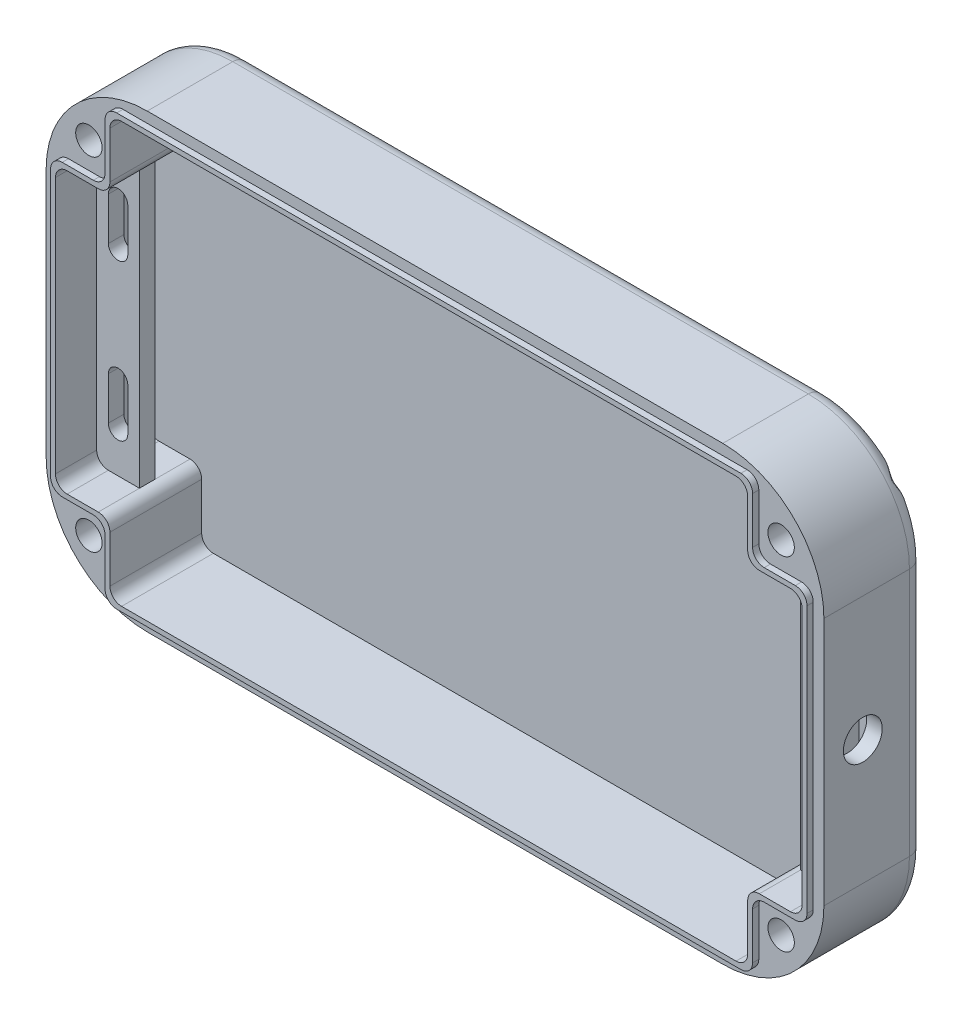
SolidWorks part; units mm, degrees
ref_plane "Спереди" through (0, 0, 0) normal (0, 0, 1) x (1, 0, 0)
ref_plane "Сверху" through (0, 0, 0) normal (0, 1, 0) x (1, 0, 0)
ref_plane "Справа" through (0, 0, 0) normal (1, 0, 0) x (0, 0, -1)
sketch "Sketch1" plane through (0, 0, 0) normal (0, 0, 1) x (1, 0, 0)
  line L1 (-50, 58) -> (50, 58) construction
  line L2 (-50, 58) -> (-50, 0) construction
  line L3 (-50, 0) -> (50, 0) construction
  line L5 (-50, 29) -> (30, 29) construction
  line L7 (0, 0) -> (0, 58) construction
  line L10 (-50, 58) -> (-50, 0) construction
  line L11 (-50, 58) -> (50, 58)
  line L12 (50, 58) -> (50, 0) construction
  line L13 (50, 0) -> (-50, 0)
  line L20 (50, 0) -> (50, 19)
  line L21 (50, 19) -> (50, 58)
  line L22 (-50, 0) -> (-50, 19)
  line L23 (-50, 19) -> (-50, 58)
  dimension "D1" = 100
  dimension "D2" = 58
extrude "Boss-Extrude1" add sketch "Sketch1" along normal blind 13
shell "Shell1" thickness 2 removed face at (0, 29, 13)
sketch "Sketch3" plane through (0, 0, 2) normal (0, 0, 1) x (1, 0, 0)
  line L0 (0, 0) -> (0, 58) construction
  line L1 (48, 2) -> (41, 2)
  line L2 (48, 2) -> (48, 11)
  line L3 (48, 11) -> (41, 11)
  line L4 (41, 2) -> (41, 11)
  line L5 (-50, 0) -> (50, 0) construction
  line L6 (50, 58) -> (-50, 58) construction
  line L7 (-41, 2) -> (-41, 11)
  line L8 (48, 2) -> (48, 56) construction
  line L9 (48, 29) -> (-48, 29) construction
  line L10 (-48, 56) -> (-48, 2) construction
  line L11 (-48, 11) -> (-41, 11)
  line L12 (-48, 2) -> (-48, 11)
  line L13 (-48, 2) -> (-41, 2)
  line L14 (-48, 56) -> (-41, 56)
  line L15 (-48, 56) -> (-48, 47)
  line L16 (-48, 47) -> (-41, 47)
  line L17 (-41, 56) -> (-41, 47)
  line L18 (41, 56) -> (41, 47)
  line L19 (48, 47) -> (41, 47)
  line L20 (48, 56) -> (48, 47)
  line L21 (48, 56) -> (41, 56)
  line L22 (50, 0) -> (50, 58) construction
  circle A0 centre (44.5, 7) radius 1.7
  circle A1 centre (-44.5, 7) radius 1.7
  circle A2 centre (-44.5, 51) radius 1.7
  circle A3 centre (44.5, 51) radius 1.7
  dimension "D3" = 3.4
  dimension "D1" = 7
  dimension "D2" = 9
  dimension "D4" = 7
  dimension "D5" = 5.5
extrude "Boss-Extrude3" add sketch "Sketch3" along normal up to surface (11 mm away) up to face at (0, 29, 13)
sketch "Sketch5" plane through (0, 0, 13) normal (0, 0, 1) x (1, 0, 0)
  line L0 (0, 0) -> (0, 58) construction
  line L1 (-50, 0) -> (50, 0) construction
  line L2 (50, 58) -> (-50, 58) construction
  line L4 (48, 11) -> (48, 47) construction
  line L5 (48, 29) -> (-48, 29) construction
  line L6 (48, 11) -> (48, 47) construction
  line L7 (48.6274, 10.3726) -> (48.6274, 55.5082) construction
  line L8 (48, 11) -> (41, 11)
  line L9 (41, 11) -> (41, 2)
  line L10 (41, 2) -> (0, 2)
  line L11 (-41, 2) -> (41, 2) construction
  line L42 (48, 11) -> (48, 29)
  line L49 (48.6274, 10.3726) -> (41.6274, 10.3726)
  line L50 (41.6274, 10.3726) -> (41.6274, 1.3726)
  line L51 (41.6274, 1.3726) -> (0, 1.3726)
  line L52 (-41.6274, 1.3726) -> (0, 1.3726)
  line L53 (-41.6274, 10.3726) -> (-41.6274, 1.3726)
  line L54 (-48.6274, 10.3726) -> (-41.6274, 10.3726)
  line L58 (-48, 11) -> (-48, 29)
  line L61 (-41, 2) -> (0, 2)
  line L62 (-41, 11) -> (-41, 2)
  line L63 (-48, 11) -> (-41, 11)
  line L64 (-48, 47) -> (-41, 47)
  line L65 (-41, 47) -> (-41, 56)
  line L66 (-41, 56) -> (0, 56)
  line L68 (-48, 47) -> (-48, 29)
  line L70 (-48.6274, 47.6274) -> (-48.6274, 10.3726)
  line L71 (-48.6274, 47.6274) -> (-41.6274, 47.6274)
  line L72 (-41.6274, 47.6274) -> (-41.6274, 56.6274)
  line L73 (-41.6274, 56.6274) -> (0, 56.6274)
  line L74 (41.6274, 56.6274) -> (0, 56.6274)
  line L75 (41.6274, 47.6274) -> (41.6274, 56.6274)
  line L76 (48.6274, 47.6274) -> (41.6274, 47.6274)
  line L77 (48.6274, 47.6274) -> (48.6274, 10.3726)
  line L80 (48, 47) -> (48, 29)
  line L83 (41, 56) -> (0, 56)
  line L84 (41, 47) -> (41, 56)
  line L85 (48, 47) -> (41, 47)
  line L86 (42.6274, -71.1638) -> (42.6274, 29) construction
  line L87 (48.6274, 55.5082) -> (42.6274, -71.1638) construction
  line L88 (48, 29) -> (42, -97.6721) construction
  line L89 (42, -97.6721) -> (42, 29) construction
  line L90 (50, 58) -> (-50, 58) construction
  dimension "D1" = 29
extrude "Boss-Extrude4" add sketch "Sketch5" along normal blind 0.8
fillet "Fillet6" radius 1.5 12 edges at (-41, 2, 7.9) (-41, 11, 7.9) (-48, 11, 7.9) (-48, 47, 7.9) (-41, 47, 7.9) (-41, 56, 7.9) (41, 56, 7.9) (41, 47, 7.9) (48, 47, 7.9) (41, 2, 7.9) (48, 11, 7.9) (41, 11, 7.9)
fillet "Fillet7" radius 1.5 12 edges at (41.6274, 10.3726, 13.4) (41.6274, 1.3726, 13.4) (-41.6274, 1.3726, 13.4) (-41.6274, 10.3726, 13.4) (-48.6274, 47.6274, 13.4) (-41.6274, 47.6274, 13.4) (-41.6274, 56.6274, 13.4) (41.6274, 56.6274, 13.4) (41.6274, 47.6274, 13.4) (48.6274, 47.6274, 13.4) (-48.6274, 10.3726, 13.4) (48.6274, 10.3726, 13.4)
sketch "Sketch6" plane through (50, 0, 0) normal (1, 0, 0) x (0, 0, -1)
  line L5 (-13, 0) -> (0, 0) construction
  line L7 (-13, 0) -> (-13, 58) construction
  circle A0 centre (-8, 29) radius 2.5
  dimension "D11" = 5
  dimension "D2" = 29
  dimension "D3" = 5
extrude "Cut-Extrude1" cut sketch "Sketch6" against normal blind 10
fillet "Fillet8" radius 13 4 edges at (-50, 0, 6.5) (-50, 58, 6.5) (50, 58, 6.5) (50, 0, 6.5)
fillet "Fillet11" radius 2 8 edges at (46.1924, 54.1924, 0) (50, 29, 0) (46.1924, 3.8076, 0) (0, 0, 0) (-46.1924, 3.8076, 0) (-50, 29, 0) (-46.1924, 54.1924, 0) (0, 58, 0)
ref_plane "Plane1" through (0, 29, 0) normal (0, -1, 0) x (-1, 0, 0)
ref_plane "Plane2" through (0, 0, 0) normal (1, 0, 0) x (0, 0, -1)
ref_plane "Plane3" through (0, 0, 7.5) normal (0, 0, 1) x (1, 0, 0)
sketch "Sketch14" plane through (0, 0, 7.5) normal (0, 0, 1) x (1, 0, 0)
  line L6 (48, 12.5) -> (48, 45.5)
  line L25 (48, 12.5) -> (48, 45.5) construction
  line L26 (46.5, 11) -> (42.5, 11)
  line L27 (42.5, 11) -> (42.5, 47)
  line L28 (42.5, 47) -> (46.5, 47)
  line L29 (45.25, 16.25) -> (45.25, 21.75) construction
  line L30 (44, 16.25) -> (44, 21.75)
  line L31 (46.5, 16.25) -> (46.5, 21.75)
  line L32 (42.5, 29) -> (48, 29) construction
  line L33 (45.25, 41.75) -> (45.25, 36.25) construction
  line L34 (44, 41.75) -> (44, 36.25)
  line L35 (46.5, 41.75) -> (46.5, 36.25)
  line L36 (0, 0) -> (0, 58) construction
  line L37 (-37, 0) -> (37, 0) construction
  line L38 (37, 58) -> (-37, 58) construction
  line L39 (-42.5, 29) -> (-48, 29) construction
  line L40 (-42.5, 47) -> (-46.5, 47)
  line L41 (-42.5, 11) -> (-42.5, 47)
  line L42 (-46.5, 11) -> (-42.5, 11)
  line L43 (-48, 12.5) -> (-48, 45.5)
  line L44 (-45.25, 41.75) -> (-45.25, 36.25) construction
  line L45 (-44, 41.75) -> (-44, 36.25)
  line L46 (-46.5, 41.75) -> (-46.5, 36.25)
  line L47 (-45.25, 16.25) -> (-45.25, 21.75) construction
  line L48 (-44, 16.25) -> (-44, 21.75)
  line L49 (-46.5, 16.25) -> (-46.5, 21.75)
  arc A0 (48, 45.5) -> (46.5, 47) centre (46.5, 45.5) ccw construction
  arc A1 (46.5, 47) -> (48, 45.5) centre (46.5, 45.5) cw
  arc A2 (46.5, 11) -> (48, 12.5) centre (46.5, 12.5) ccw
  arc A3 (44, 16.25) -> (46.5, 16.25) centre (45.25, 16.25) ccw
  arc A4 (46.5, 21.75) -> (44, 21.75) centre (45.25, 21.75) ccw
  arc A5 (44, 41.75) -> (46.5, 41.75) centre (45.25, 41.75) cw
  arc A6 (46.5, 36.25) -> (44, 36.25) centre (45.25, 36.25) cw
  arc A7 (-46.5, 11) -> (-48, 12.5) centre (-46.5, 12.5) cw
  arc A8 (-46.5, 47) -> (-48, 45.5) centre (-46.5, 45.5) ccw
  arc A9 (-44, 41.75) -> (-46.5, 41.75) centre (-45.25, 41.75) ccw
  arc A10 (-46.5, 36.25) -> (-44, 36.25) centre (-45.25, 36.25) ccw
  arc A11 (-44, 16.25) -> (-46.5, 16.25) centre (-45.25, 16.25) cw
  arc A12 (-46.5, 21.75) -> (-44, 21.75) centre (-45.25, 21.75) cw
  point P15 (45.25, 19)
  point P20 (45.25, 15)
  point P21 (45.25, 23)
  point P26 (45.25, 39)
  point P31 (45.25, 35)
  point P32 (45.25, 43)
  point P49 (-45.25, 43)
  point P50 (-45.25, 35)
  point P53 (-45.25, 39)
  point P58 (-45.25, 23)
  point P59 (-45.25, 15)
  point P62 (-45.25, 19)
  dimension "D1" = 2.75
  dimension "D2" = 8
  dimension "D3" = 2.5
  dimension "D4" = 4
extrude "Boss-Extrude8" add sketch "Sketch14" against normal mid plane 2
sketch "Sketch17" plane through (0, 0, 0) normal (0, 0, -1) x (-1, 0, 0)
  line L0 (0, 0) -> (0, 58) construction
  line L2 (-37, 58) -> (37, 58) construction
  line L3 (0, 58) -> (48, 29) construction
  line L4 (48, 29) -> (-48, 29) construction
  line L5 (37, 0) -> (-37, 0) construction
  circle A0 centre (44.5, 7) radius 1.7
  circle A1 centre (-44.5, 7) radius 1.7
  circle A2 centre (-44.5, 51) radius 1.7
  circle A3 centre (44.5, 51) radius 1.7
  dimension "D1" = 3.4
extrude "Cut-Extrude5" cut sketch "Sketch17" against normal blind 10
sketch "Sketch18" plane through (0, 0, 0) normal (0, 0, -1) x (-1, 0, 0)
  line L0 (0, 0) -> (0, 58) construction
  line L1 (-50, 13) -> (-50, 45) construction
  line L2 (-37, 58) -> (37, 58) construction
  line L4 (50, 45) -> (50, 13) construction
  line L5 (50, 29) -> (-50, 29) construction
  circle A0 centre (44.5, 7) radius 2.5
  circle A1 centre (-44.5, 7) radius 2.5
  circle A2 centre (-44.5, 51) radius 2.5
  circle A3 centre (44.5, 51) radius 2.5
  dimension "D1" = 5
extrude "Cut-Extrude6" cut sketch "Sketch18" against normal blind 5
fillet "Fillet16" radius 0.4 8 edges at (-46.8011, 51.9773, 0.2862) (-45.9586, 4.9696, 0.2862) (-42.5478, 8.5617, 0) (46.8011, 6.0227, 0.2862) (42.5478, 49.4383, 0) (-42.5478, 49.4383, 0) (42.5478, 8.5617, 0) (45.9586, 53.0304, 0.2862)
ref_plane "Plane4" through (0, 19, 0) normal (0, -1, 0) x (-1, 0, 0)
ref_plane "Plane5" through (0, 0, 0) normal (1, 0, 0) x (0, 0, -1)
